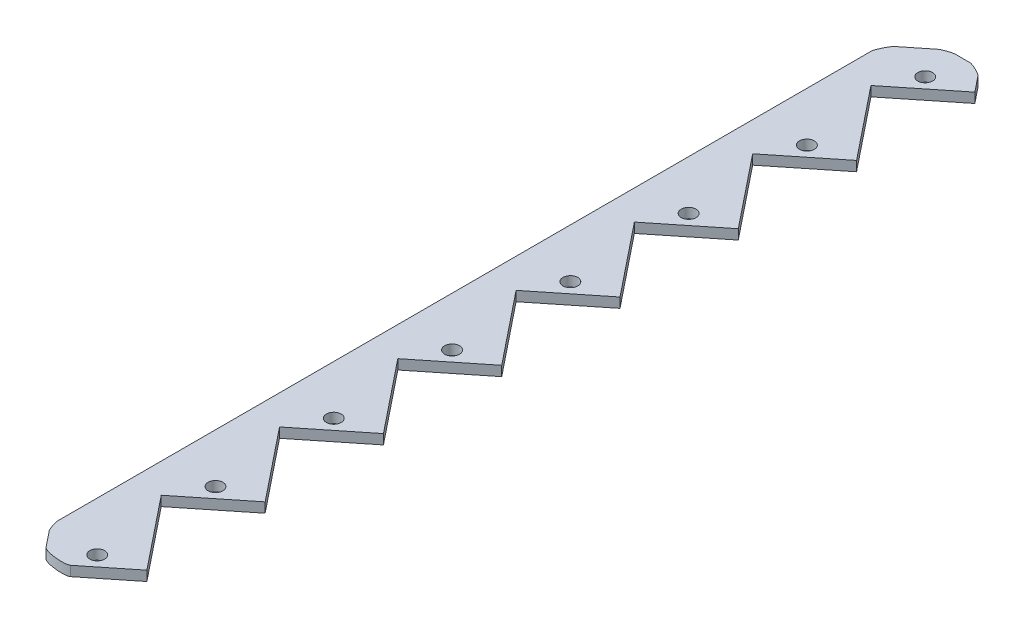
SolidWorks part; units mm, degrees
ref_plane "Front Plane" through (0, 0, 0) normal (0, 0, 1) x (1, 0, 0)
ref_plane "Top Plane" through (0, 0, 0) normal (0, 1, 0) x (1, 0, 0)
ref_plane "Right Plane" through (0, 0, 0) normal (1, 0, 0) x (0, 0, -1)
sketch "Sketch1" plane through (0, 0, 0) normal (0, 1, 0) x (1, 0, 0)
  line L0 (-13.635, -43.1454) -> (0.2556, -60.4948) construction
  line L5 (-13.635, -43.1454) -> (-22.9293, -50.5868) construction
  line L6 (-22.9293, -50.5868) -> (-9.0387, -67.9362) construction
  line L7 (-22.1678, 36.7724) -> (28.6322, 36.7724) construction
  line L8 (-22.1678, 36.7724) -> (-22.1678, -191.8276) construction
  line L9 (-22.1678, -191.8276) -> (28.6322, -191.8276) construction
  line L10 (28.6322, 36.7724) -> (28.6322, -191.8276) construction
  line L11 (0.2556, -60.4948) -> (-9.0387, -67.9362) construction
  line L12 (-13.635, -24.0954) -> (0.2556, -41.4448) construction
  line L13 (-13.635, -24.0954) -> (-22.9293, -31.5368) construction
  line L14 (-22.9293, -31.5368) -> (-9.0387, -48.8862) construction
  line L15 (-8.1122, -59.5683) -> (-27.1622, -59.5683) construction
  line L16 (-8.1122, -59.5683) -> (-8.1122, -40.5183) construction
  line L17 (0.2556, -41.4448) -> (-9.0387, -48.8862) construction
  line L18 (-8.1122, -40.5183) -> (-27.1622, -40.5183) construction
  line L19 (-8.1122, -40.5183) -> (-8.1122, -21.4683) construction
  line L20 (-13.635, -100.2954) -> (0.2556, -117.6448) construction
  line L21 (-13.635, -100.2954) -> (-22.9293, -107.7368) construction
  line L22 (-22.9293, -107.7368) -> (-9.0387, -125.0862) construction
  line L23 (0.2556, -117.6448) -> (-9.0387, -125.0862) construction
  line L24 (-13.635, -81.2454) -> (0.2556, -98.5948) construction
  line L25 (-13.635, -81.2454) -> (-22.9293, -88.6868) construction
  line L26 (-22.9293, -88.6868) -> (-9.0387, -106.0362) construction
  line L27 (-8.1122, -116.7183) -> (-27.1622, -116.7183) construction
  line L28 (-8.1122, -116.7183) -> (-8.1122, -97.6683) construction
  line L29 (0.2556, -98.5948) -> (-9.0387, -106.0362) construction
  line L30 (-8.1122, -97.6683) -> (-27.1622, -97.6683) construction
  line L31 (-8.1122, -97.6683) -> (-8.1122, -78.6183) construction
  line L32 (-13.635, -5.0454) -> (0.2556, -22.3948) construction
  line L33 (-13.635, -5.0454) -> (-22.9293, -12.4868) construction
  line L34 (-13.635, 14.0046) -> (0.2556, -3.3448) construction
  line L35 (-13.635, 14.0046) -> (-22.9293, 6.5632) construction
  line L36 (-22.9293, 6.5632) -> (-9.0387, -10.7862) construction
  line L37 (0.2556, -3.3448) -> (-9.0387, -10.7862) construction
  line L38 (-22.9293, -12.4868) -> (-9.0387, -29.8362) construction
  line L39 (0.2556, -22.3948) -> (-9.0387, -29.8362) construction
  line L40 (-13.635, 33.0546) -> (0.2556, 15.7052) construction
  line L41 (-13.635, 33.0546) -> (-22.9293, 25.6132) construction
  line L42 (-22.9293, 25.6132) -> (-9.0387, 8.2638) construction
  line L43 (0.2556, 15.7052) -> (-9.0387, 8.2638) construction
  line L44 (-8.1122, -21.4683) -> (-27.1622, -21.4683) construction
  line L45 (-8.1122, -21.4683) -> (-8.1122, -2.4183) construction
  line L46 (-13.635, -62.1954) -> (0.2556, -79.5448) construction
  line L47 (-13.635, -62.1954) -> (-22.9293, -69.6368) construction
  line L48 (-22.9293, -69.6368) -> (-9.0387, -86.9862) construction
  line L49 (0.2556, -79.5448) -> (-9.0387, -86.9862) construction
  line L50 (-8.1122, -78.6183) -> (-27.1622, -78.6183) construction
  line L51 (-8.1122, -78.6183) -> (-8.1122, -59.5683) construction
  line L52 (-8.1122, -2.4183) -> (-27.1622, -2.4183) construction
  line L53 (-8.1122, -2.4183) -> (-8.1122, 16.6317) construction
  line L54 (-8.1122, 16.6317) -> (-27.1622, 16.6317) construction
  line L55 (-8.1122, 16.6317) -> (-8.1122, 35.6817) construction
  line L56 (-22.9293, 25.6132) -> (-25.9059, 29.3309) construction
  line L57 (-25.9059, 29.3309) -> (-16.6116, 36.7724) construction
  line L58 (-16.6116, 36.7724) -> (-13.635, 33.0546) construction
  line L59 (-24.4176, 27.4721) -> (-15.1233, 34.9135) construction
  line L60 (-25.9059, 28.8165) -> (-25.9059, 40.1202) construction
  line L61 (-9.0387, 8.2638) -> (-6.0621, 4.5461) construction
  line L62 (-8.1122, 36.5878) -> (-8.1122, -24.5097) construction
  line L63 (-6.0621, 4.5461) -> (3.2322, 11.9875) construction
  line L64 (0.2556, 15.7052) -> (3.2322, 11.9875) construction
  line L65 (1.7439, 13.8464) -> (-7.5504, 6.405) construction
  line L66 (-19.7704, 30.6783) -> (-19.7704, 38.979) construction
  line L67 (-2.9032, 9.6112) -> (-2.9032, 17.9119) construction
  line L68 (3.2322, 11.4731) -> (3.2322, 48.1829) construction
  line L69 (4.7205, 13.8464) -> (14.0148, 6.405) construction
  line L70 (6.2088, 15.7052) -> (3.2322, 11.9875) construction
  line L71 (12.5265, 4.5461) -> (3.2322, 11.9875) construction
  line L72 (15.5031, 8.2638) -> (12.5265, 4.5461) construction
  line L73 (30.882, 27.4721) -> (21.5877, 34.9135) construction
  line L74 (23.0759, 36.7724) -> (20.0994, 33.0546) construction
  line L75 (32.3703, 29.3309) -> (23.0759, 36.7724) construction
  line L76 (29.3937, 25.6132) -> (32.3703, 29.3309) construction
  line L77 (14.5766, 16.6317) -> (14.5766, 35.6817) construction
  line L78 (14.5766, 16.6317) -> (33.6266, 16.6317) construction
  line L79 (14.5766, -2.4183) -> (14.5766, 16.6317) construction
  line L80 (14.5766, -2.4183) -> (33.6266, -2.4183) construction
  line L81 (14.5766, -78.6183) -> (14.5766, -59.5683) construction
  line L82 (14.5766, -78.6183) -> (33.6266, -78.6183) construction
  line L83 (6.2088, -79.5448) -> (15.5031, -86.9862) construction
  line L84 (29.3937, -69.6368) -> (15.5031, -86.9862) construction
  line L85 (20.0994, -62.1954) -> (29.3937, -69.6368) construction
  line L86 (20.0994, -62.1954) -> (6.2088, -79.5448) construction
  line L87 (14.5766, -21.4683) -> (14.5766, -2.4183) construction
  line L88 (14.5766, -21.4683) -> (33.6266, -21.4683) construction
  line L89 (6.2088, 15.7052) -> (15.5031, 8.2638) construction
  line L90 (29.3937, 25.6132) -> (15.5031, 8.2638) construction
  line L91 (20.0994, 33.0546) -> (29.3937, 25.6132) construction
  line L92 (20.0994, 33.0546) -> (6.2088, 15.7052) construction
  line L93 (6.2088, -22.3948) -> (15.5031, -29.8362) construction
  line L94 (29.3937, -12.4868) -> (15.5031, -29.8362) construction
  line L95 (6.2088, -3.3448) -> (15.5031, -10.7862) construction
  line L96 (29.3937, 6.5632) -> (15.5031, -10.7862) construction
  line L97 (20.0994, 14.0046) -> (29.3937, 6.5632) construction
  line L98 (20.0994, 14.0046) -> (6.2088, -3.3448) construction
  line L99 (20.0994, -5.0454) -> (29.3937, -12.4868) construction
  line L100 (20.0994, -5.0454) -> (6.2088, -22.3948) construction
  line L101 (14.5766, -97.6683) -> (14.5766, -78.6183) construction
  line L102 (14.5766, -97.6683) -> (33.6266, -97.6683) construction
  line L103 (6.2088, -98.5948) -> (15.5031, -106.0362) construction
  line L104 (14.5766, -116.7183) -> (14.5766, -97.6683) construction
  line L105 (14.5766, -116.7183) -> (33.6266, -116.7183) construction
  line L106 (29.3937, -88.6868) -> (15.5031, -106.0362) construction
  line L107 (20.0994, -81.2454) -> (29.3937, -88.6868) construction
  line L108 (20.0994, -81.2454) -> (6.2088, -98.5948) construction
  line L109 (6.2088, -117.6448) -> (15.5031, -125.0862) construction
  line L110 (29.3937, -107.7368) -> (15.5031, -125.0862) construction
  line L111 (20.0994, -100.2954) -> (29.3937, -107.7368) construction
  line L112 (20.0994, -100.2954) -> (6.2088, -117.6448) construction
  line L113 (14.5766, -40.5183) -> (14.5766, -21.4683) construction
  line L114 (14.5766, -40.5183) -> (33.6266, -40.5183) construction
  line L115 (6.2088, -41.4448) -> (15.5031, -48.8862) construction
  line L116 (14.5766, -59.5683) -> (14.5766, -40.5183) construction
  line L117 (14.5766, -59.5683) -> (33.6266, -59.5683) construction
  line L118 (29.3937, -31.5368) -> (15.5031, -48.8862) construction
  line L119 (20.0994, -24.0954) -> (29.3937, -31.5368) construction
  line L120 (20.0994, -24.0954) -> (6.2088, -41.4448) construction
  line L121 (6.2088, -60.4948) -> (15.5031, -67.9362) construction
  line L122 (29.3937, -50.5868) -> (15.5031, -67.9362) construction
  line L123 (20.0994, -43.1454) -> (29.3937, -50.5868) construction
  line L124 (20.0994, -43.1454) -> (6.2088, -60.4948) construction
  line L125 (23.0759, 36.7724) -> (-16.6116, 36.7724) construction
  circle A2 centre (-8.1122, -59.5683) radius 5.9531 construction
  circle A3 centre (-8.1122, -59.5683) radius 19.05 construction
  circle A4 centre (-8.1122, -40.5183) radius 5.9531 construction
  circle A5 centre (-8.1122, -40.5183) radius 19.05 construction
  circle A6 centre (-8.1122, -116.7183) radius 5.9531 construction
  circle A7 centre (-8.1122, -116.7183) radius 19.05 construction
  circle A8 centre (-8.1122, -97.6683) radius 5.9531 construction
  circle A9 centre (-8.1122, -97.6683) radius 19.05 construction
  circle A10 centre (-8.1122, -2.4183) radius 5.9531 construction
  circle A11 centre (-8.1122, -2.4183) radius 19.05 construction
  circle A12 centre (-8.1122, 16.6317) radius 5.9531 construction
  circle A13 centre (-8.1122, 16.6317) radius 19.05 construction
  circle A14 centre (-8.1122, -21.4683) radius 5.9531 construction
  circle A15 centre (-8.1122, -21.4683) radius 19.05 construction
  circle A16 centre (-8.1122, -78.6183) radius 5.9531 construction
  circle A17 centre (-8.1122, -78.6183) radius 19.05 construction
  circle A18 centre (-19.7704, 31.1928) radius 1.1906
  circle A19 centre (-2.9032, 10.1257) radius 1.1906
  circle A20 centre (14.5766, -78.6183) radius 19.05 construction
  circle A21 centre (14.5766, -78.6183) radius 5.9531 construction
  circle A22 centre (14.5766, -21.4683) radius 19.05 construction
  circle A23 centre (14.5766, -21.4683) radius 5.9531 construction
  circle A24 centre (14.5766, 16.6317) radius 19.05 construction
  circle A25 centre (14.5766, 16.6317) radius 5.9531 construction
  circle A26 centre (14.5766, -2.4183) radius 19.05 construction
  circle A27 centre (14.5766, -2.4183) radius 5.9531 construction
  circle A28 centre (14.5766, -97.6683) radius 19.05 construction
  circle A29 centre (14.5766, -97.6683) radius 5.9531 construction
  circle A30 centre (14.5766, -116.7183) radius 19.05 construction
  circle A31 centre (14.5766, -116.7183) radius 5.9531 construction
  circle A32 centre (14.5766, -40.5183) radius 19.05 construction
  circle A33 centre (14.5766, -40.5183) radius 5.9531 construction
  circle A34 centre (14.5766, -59.5683) radius 19.05 construction
  circle A35 centre (14.5766, -59.5683) radius 5.9531 construction
  circle A36 centre (9.3676, 10.1257) radius 1.1906
  circle A37 centre (26.2348, 31.1928) radius 1.1906
  point P81 (-15.1233, 34.9135)
  point P97 (3.2322, 36.7724)
  dimension "D3" = 2.3813
  dimension "D23" = 38.1
  dimension "D1" = 4.7625
  dimension "D4" = 50.8
  dimension "D5" = 228.6
  dimension "D21" = 22.225
  dimension "D22" = 11.9062
sketch "Sketch2" plane through (0, 0, 0) normal (0, 1, 0) x (1, 0, 0)
  line L0 (-16.6116, 36.7724) -> (-13.635, 33.0546)
  line L1 (-13.635, 33.0546) -> (-22.9293, 25.6132)
  line L2 (-22.9293, 25.6132) -> (-13.635, 14.0046)
  line L3 (-18.2822, 10.2839) -> (-19.7704, 12.1428)
  line L4 (-13.635, 14.0046) -> (-22.9293, 6.5632) construction
  line L5 (-19.7704, -199969.3217) -> (-19.7704, 200038.979) construction
  line L6 (3.2322, 37.6418) -> (3.2322, 34.7632) construction
  line L7 (-9.0387, -10.7862) -> (0.2556, -22.3948)
  line L8 (3.2322, -199988.5269) -> (3.2322, 200048.1829) construction
  line L9 (-13.635, 14.0046) -> (-22.9293, 6.5632)
  line L10 (-22.9293, 6.5632) -> (-13.635, -5.0454)
  line L11 (-13.635, -5.0454) -> (-22.9293, -12.4868)
  line L12 (-22.9293, -12.4868) -> (-13.635, -24.0954)
  line L13 (-13.635, -24.0954) -> (-22.9293, -31.5368)
  line L14 (-22.9293, -31.5368) -> (-13.635, -43.1454)
  line L15 (-13.635, -43.1454) -> (-22.9293, -50.5868)
  line L16 (-22.9293, -50.5868) -> (-13.635, -62.1954)
  line L17 (-13.635, -62.1954) -> (-22.9293, -69.6368)
  line L18 (-22.9293, -69.6368) -> (-13.635, -81.2454)
  line L19 (-13.635, -81.2454) -> (-22.9293, -88.6868)
  line L20 (-22.9293, -88.6868) -> (-13.635, -100.2954)
  line L21 (-13.635, -100.2954) -> (-22.9293, -107.7368)
  line L22 (-22.9293, -107.7368) -> (-13.635, -119.3454)
  line L23 (0.2556, 15.7052) -> (-9.0387, 8.2638)
  line L24 (-9.0387, 8.2638) -> (0.2556, -3.3448)
  line L25 (0.2556, -3.3448) -> (-9.0387, -10.7862)
  line L26 (-9.0387, -29.8362) -> (0.2556, -41.4448)
  line L27 (0.2556, -22.3948) -> (-9.0387, -29.8362)
  line L28 (-9.0387, -48.8862) -> (0.2556, -60.4948)
  line L29 (0.2556, -41.4448) -> (-9.0387, -48.8862)
  line L30 (-9.0387, -67.9362) -> (0.2556, -79.5448)
  line L31 (0.2556, -60.4948) -> (-9.0387, -67.9362)
  line L32 (-9.0387, -86.9862) -> (0.2556, -98.5948)
  line L33 (0.2556, -79.5448) -> (-9.0387, -86.9862)
  line L34 (-9.0387, -106.0362) -> (0.2556, -117.6448)
  line L35 (0.2556, -98.5948) -> (-9.0387, -106.0362)
  line L37 (0.2556, -117.6448) -> (-9.0387, -125.0862)
  line L38 (6.2088, -117.6448) -> (15.5031, -125.0862)
  line L39 (-9.0387, -125.0862) -> (0.2556, -136.6948) [skipped]
  line L41 (-22.9293, 25.6132) -> (-27.6918, 25.6132) construction
  line L42 (-16.6116, 36.7724) -> (-27.6918, 36.7724)
  line L43 (-27.6918, 36.7724) -> (-27.6918, -124.1079)
  line L44 (-13.635, -119.3454) -> (-13.635, -124.1079)
  line L45 (-13.635, -124.1079) -> (-27.6918, -124.1079)
  line L47 (6.2088, -98.5948) -> (15.5031, -106.0362)
  line L48 (15.5031, -106.0362) -> (6.2088, -117.6448)
  line L49 (6.2088, -79.5448) -> (15.5031, -86.9862)
  line L50 (15.5031, -86.9862) -> (6.2088, -98.5948)
  line L51 (6.2088, -60.4948) -> (15.5031, -67.9362)
  line L52 (15.5031, -67.9362) -> (6.2088, -79.5448)
  line L53 (6.2088, -41.4448) -> (15.5031, -48.8862)
  line L54 (15.5031, -48.8862) -> (6.2088, -60.4948)
  line L55 (6.2088, -22.3948) -> (15.5031, -29.8362)
  line L56 (15.5031, -29.8362) -> (6.2088, -41.4448)
  line L57 (6.2088, -3.3448) -> (15.5031, -10.7862)
  line L58 (15.5031, 8.2638) -> (6.2088, -3.3448)
  line L59 (6.2088, 15.7052) -> (15.5031, 8.2638)
  line L60 (15.5031, -10.7862) -> (6.2088, -22.3948)
  line L61 (0.2556, 15.7052) -> (6.2088, 15.7052)
  line L62 (29.3937, 25.6132) -> (34.1562, 25.6132) construction
  line L63 (20.0994, -124.1079) -> (34.1562, -124.1079)
  line L64 (20.0994, -119.3454) -> (20.0994, -124.1079)
  line L65 (34.1562, 36.7724) -> (34.1562, -124.1079)
  line L66 (23.0759, 36.7724) -> (34.1562, 36.7724)
  line L67 (29.3937, -107.7368) -> (20.0994, -119.3454)
  line L68 (20.0994, -100.2954) -> (29.3937, -107.7368)
  line L69 (29.3937, -88.6868) -> (20.0994, -100.2954)
  line L70 (20.0994, -81.2454) -> (29.3937, -88.6868)
  line L71 (29.3937, -69.6368) -> (20.0994, -81.2454)
  line L72 (20.0994, -62.1954) -> (29.3937, -69.6368)
  line L73 (29.3937, -50.5868) -> (20.0994, -62.1954)
  line L74 (20.0994, -43.1454) -> (29.3937, -50.5868)
  line L75 (29.3937, -31.5368) -> (20.0994, -43.1454)
  line L76 (20.0994, -24.0954) -> (29.3937, -31.5368)
  line L77 (29.3937, -12.4868) -> (20.0994, -24.0954)
  line L78 (20.0994, -5.0454) -> (29.3937, -12.4868)
  line L79 (29.3937, 6.5632) -> (20.0994, -5.0454)
  line L80 (20.0994, 14.0046) -> (29.3937, 6.5632)
  line L81 (24.7465, 10.2839) -> (26.2348, 12.1428)
  line L82 (29.3937, 25.6132) -> (20.0994, 14.0046)
  line L83 (20.0994, 33.0546) -> (29.3937, 25.6132)
  line L84 (23.0759, 36.7724) -> (20.0994, 33.0546)
  line L85 (-27.6918, 31.9683) -> (-21.6916, 36.7724)
  line L86 (28.1559, 36.7724) -> (34.1562, 31.9683)
  line L87 (-22.9293, -107.7368) -> (-27.6918, -101.7884)
  line L88 (29.3937, -107.7368) -> (34.1562, -101.7884)
  line L89 (-9.0387, -125.0862) -> (-6.0621, -128.8039)
  line L90 (15.5031, -125.0862) -> (12.5265, -128.8039)
  line L91 (-6.0621, -128.8039) -> (12.5265, -128.8039)
  line L92 (-25.9059, 29.3309) -> (-16.6116, 36.7724) construction
  line L93 (32.3703, 29.3309) -> (23.0759, 36.7724) construction
  circle A0 centre (-19.7704, 31.1928) radius 1.1906
  circle A1 centre (-19.7704, 31.1928) radius 1.1906 construction
  circle A2 centre (-19.7704, 12.1428) radius 1.1906
  circle A3 centre (-19.7704, -6.9072) radius 1.1906
  circle A4 centre (-19.7704, -25.9572) radius 1.1906
  circle A5 centre (-19.7704, -45.0072) radius 1.1906
  circle A6 centre (-19.7704, -64.0572) radius 1.1906
  circle A7 centre (-19.7704, -83.1072) radius 1.1906
  circle A8 centre (-19.7704, -102.1572) radius 1.1906
  circle A9 centre (-2.9032, 10.1257) radius 1.1906
  circle A10 centre (-2.9032, 10.1257) radius 1.1906 construction
  circle A11 centre (-2.9032, -8.9243) radius 1.1906
  circle A12 centre (-2.9032, -27.9743) radius 1.1906
  circle A13 centre (-2.9032, -47.0243) radius 1.1906
  circle A14 centre (-2.9032, -66.0743) radius 1.1906
  circle A15 centre (-2.9032, -85.1243) radius 1.1906
  circle A16 centre (-2.9032, -104.1743) radius 1.1906
  circle A17 centre (-2.9032, -123.2243) radius 1.1906
  circle A18 centre (9.3676, -123.2243) radius 1.1906
  circle A19 centre (9.3676, -104.1743) radius 1.1906
  circle A20 centre (9.3676, -85.1243) radius 1.1906
  circle A21 centre (9.3676, -66.0743) radius 1.1906
  circle A22 centre (9.3676, -47.0243) radius 1.1906
  circle A23 centre (9.3676, -27.9743) radius 1.1906
  circle A24 centre (9.3676, -8.9243) radius 1.1906
  circle A25 centre (9.3676, 10.1257) radius 1.1906
  circle A26 centre (26.2348, -102.1572) radius 1.1906
  circle A27 centre (26.2348, -83.1072) radius 1.1906
  circle A28 centre (26.2348, -64.0572) radius 1.1906
  circle A29 centre (26.2348, -45.0072) radius 1.1906
  circle A30 centre (26.2348, -25.9572) radius 1.1906
  circle A31 centre (26.2348, -6.9072) radius 1.1906
  circle A32 centre (26.2348, 12.1428) radius 1.1906
  circle A33 centre (26.2348, 31.1928) radius 1.1906
  dimension "D1" = 19.05
  dimension "D3" = 8
  dimension "D2" = 8
  dimension "D4" = 3.175
  dimension "D5" = 3.175
extrude "Boss-Extrude1" add sketch "Sketch2" along normal blind 1.5875 contours A2 L9 L2 L1 L0 L42 L85 L43 L87 L21 L20 L19 L18 L17 L16 L15 L14 L13 L12 L11 L10 A8 A7 A6 A5 A4 A3 A0 region at (-22.5659, 0, 35.1664)
fillet "Fillet1" radius 3.175 5 edges at (-16.6116, 0.7937, -36.7724) (-22.9293, 0.7937, 107.7368) (-27.6918, 0.7937, 101.7884) (-27.6918, 0.7937, -31.9683) (-21.6916, 0.7937, -36.7724) conic radius 10
